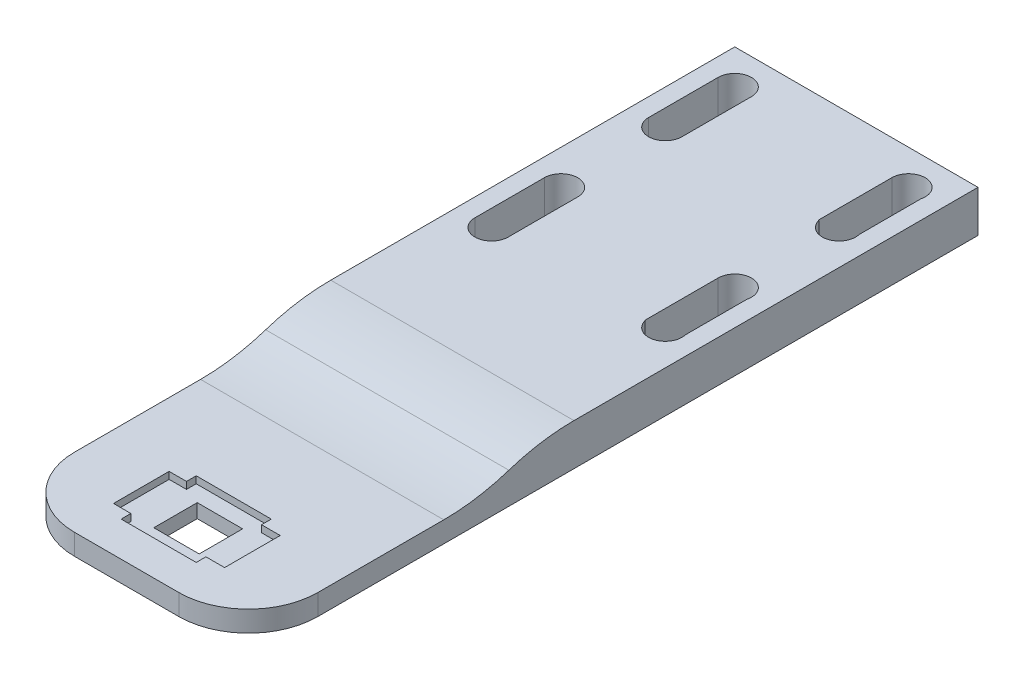
SolidWorks part; units mm, degrees
ref_plane "Front Plane" through (0, 0, 0) normal (0, 0, 1) x (1, 0, 0)
ref_plane "Top Plane" through (0, 0, 0) normal (0, 1, 0) x (1, 0, 0)
ref_plane "Right Plane" through (0, 0, 0) normal (1, 0, 0) x (0, 0, -1)
sketch "Sketch1" plane through (0, 0, 0) normal (0, 1, 0) x (1, 0, 0)
  line L1 (-17.3881, 19.9254) -> (17.6119, 19.9254)
  line L2 (-17.3881, 19.9254) -> (-17.3881, -85.0746)
  line L3 (-17.3881, -85.0746) -> (17.6119, -85.0746)
  line L4 (17.6119, 19.9254) -> (17.6119, -85.0746)
  dimension "D1" = 35
  dimension "D2" = 105
extrude "Boss-Extrude1" add sketch "Sketch1" along normal blind 6
sketch "Sketch2" plane through (0, 6, 0) normal (0, 1, 0) x (1, 0, 0)
  line L0 (17.6119, 19.9254) -> (-17.3881, 19.9254) construction
  line L1 (12.6119, -10.0746) -> (-12.3881, -10.0746)
  line L2 (12.6119, -10.0746) -> (12.6119, 14.9254)
  line L3 (12.6119, 14.9254) -> (-12.3881, 14.9254)
  line L4 (-12.3881, -10.0746) -> (-12.3881, 14.9254)
  line L5 (12.6119, -10.0746) -> (-12.3881, 14.9254) construction
  line L6 (12.6119, 14.9254) -> (-12.3881, -10.0746) construction
  point P0 (0.1119, 2.4254)
  point P7 (0.1119, 19.9254)
  dimension "D1" = 25
  dimension "D2" = 25
  dimension "D3" = 0
  dimension "D4" = 5
hole_wizard "M4 Clearance Hole1" positions "Sketch3" profile "Sketch4" hole size "M4" standard "ANSI Metric" end condition through all
sketch "Sketch3" plane through (0, 6, 0) normal (0, 1, 0) x (1, 0, 0)
  point P0 (-12.3881, 14.9254)
  point P3 (12.6119, 14.9254)
  point P6 (12.6119, -10.0746)
  point P9 (-12.3881, -10.0746)
sketch "Sketch4" plane through (-12.3881, 6, -14.9254) normal (1, 0, 0) x (0, 0, 1)
  line L0 (0, 0) -> (0, 6)
  line L1 (0, 6) -> (2.4, 6)
  line L2 (2.4, 6) -> (2.4, 0)
  line L5 (2.4, 0) -> (0, 0)
  line L11 (0, -6.35) -> (0, 107.95) construction
  dimension "Thru Hole Dia." = 4.8
  dimension "Thru Hole Depth" = 6
pattern_linear "LPattern2" count 2 spacing 10 along (0, 0, 1) of "M4 Clearance Hole1"
sketch "Sketch5" plane through (0, 6, 0) normal (0, 1, 0) x (1, 0, 0)
  line L1 (-14.7881, 14.9254) -> (-9.9881, 14.9254)
  line L2 (-14.7881, 14.9254) -> (-14.7881, 4.9254)
  line L3 (-14.7881, 4.9254) -> (-9.9881, 4.9254)
  line L4 (-9.9881, 14.9254) -> (-9.9881, 4.9254)
  line L5 (-14.7881, -10.0746) -> (-9.9881, -10.0746)
  line L6 (-14.7881, -10.0746) -> (-14.7881, -20.0746)
  line L7 (-14.7881, -20.0746) -> (-9.9881, -20.0746)
  line L8 (-9.9881, -10.0746) -> (-9.9881, -20.0746)
  line L9 (10.2119, 14.9254) -> (14.9426, 14.9254)
  line L10 (10.2119, 14.9254) -> (10.2119, 4.3527)
  line L11 (10.2119, 4.3527) -> (14.9426, 4.3527)
  line L12 (14.9426, 14.9254) -> (14.9426, 4.3527)
  line L13 (10.2119, -10.0746) -> (14.9426, -10.0746)
  line L14 (10.2119, -10.0746) -> (10.2119, -20.6473)
  line L15 (10.2119, -20.6473) -> (14.9426, -20.6473)
  line L16 (14.9426, -10.0746) -> (14.9426, -20.6473)
  circle A0 centre (-12.3881, 14.9254) radius 2.4 construction
  circle A1 centre (-12.3881, 4.9254) radius 2.4 construction
  circle A2 centre (-12.3881, -10.0746) radius 2.4 construction
  circle A3 centre (-12.3881, -20.0746) radius 2.4 construction
  circle A4 centre (12.6119, 14.9254) radius 2.4 construction
  circle A5 centre (12.6119, 4.9254) radius 2.4 construction
  circle A6 centre (12.6119, -10.0746) radius 2.4 construction
  circle A7 centre (12.6119, -20.0746) radius 2.4 construction
extrude "Cut-Extrude1" cut sketch "Sketch5" against normal through all
sketch "Sketch6" plane through (0, 6, 0) normal (0, 1, 0) x (1, 0, 0)
  line L1 (5.1119, -80.0746) -> (-5.6881, -80.0746)
  line L2 (5.1119, -80.0746) -> (5.1119, -69.2746)
  line L3 (5.1119, -69.2746) -> (-5.6881, -69.2746)
  line L4 (-5.6881, -80.0746) -> (-5.6881, -69.2746)
  line L5 (5.1119, -80.0746) -> (-5.6881, -69.2746) construction
  line L6 (5.1119, -69.2746) -> (-5.6881, -80.0746) construction
  line L9 (-17.3881, -85.0746) -> (17.6119, -85.0746) construction
  point P0 (-0.2881, -74.6746)
  dimension "D1" = 10.8
  dimension "D2" = 10.8
  dimension "D3" = 5
extrude "Cut-Extrude2" cut sketch "Sketch6" against normal offset from surface (4 mm away) 2 up to face at (-12.3881, 0, 15.0746)
sketch "Sketch7" plane through (0, 2, 0) normal (0, 1, 0) x (1, 0, 0)
  line L0 (5.1119, -80.0746) -> (5.1119, -69.2746) construction
  line L1 (3.2656, -77.8005) -> (-3.2656, -77.8005)
  line L2 (3.2656, -77.8005) -> (3.2656, -71.5487)
  line L3 (3.2656, -71.5487) -> (-3.2656, -71.5487)
  line L4 (-3.2656, -77.8005) -> (-3.2656, -71.5487)
  line L5 (3.2656, -77.8005) -> (-3.2656, -71.5487) construction
  line L6 (3.2656, -71.5487) -> (-3.2656, -77.8005) construction
  point P0 (0, -74.6746)
  point P7 (5.1119, -74.6746)
  dimension "D1" = 0
extrude "Cut-Extrude3" cut sketch "Sketch7" against normal through all
sketch "Sketch8" plane through (0, 6, 0) normal (0, 1, 0) x (1, 0, 0)
  line L0 (5.1119, -80.0746) -> (5.1119, -69.2746) construction
  line L1 (7.7965, -78.6746) -> (-8.1881, -78.6746)
  line L2 (7.7965, -78.6746) -> (7.7965, -70.6746)
  line L3 (7.7965, -70.6746) -> (-8.1881, -70.6746)
  line L4 (-8.1881, -78.6746) -> (-8.1881, -70.6746)
  line L5 (7.7965, -78.6746) -> (-8.1881, -70.6746) construction
  line L6 (7.7965, -70.6746) -> (-8.1881, -78.6746) construction
  line L7 (-5.6881, -69.2746) -> (-5.6881, -80.0746) construction
  point P0 (-0.1958, -74.6746)
  point P7 (5.1119, -74.6746)
  dimension "D1" = 0
  dimension "D2" = 2.5
  dimension "D3" = 8
extrude "Cut-Extrude4" cut sketch "Sketch8" against normal up to surface (4 mm away) up to face at (0, 2, 74.6746)
fillet "Fillet1" radius 10 2 edges at (17.6119, 3, 85.0746) (-17.3881, 3, 85.0746)
sketch "Sketch9" plane through (0, 0, 0) normal (0, -1, 0) x (1, 0, 0)
  line L0 (-17.3881, -19.9254) -> (-17.3881, 75.0746) construction
  line L1 (-17.3881, 43.8746) -> (19.6619, 43.8746)
  line L2 (-17.3881, 43.8746) -> (-17.3881, 85.0746)
  line L3 (-17.3881, 85.0746) -> (19.6619, 85.0746)
  line L4 (19.6619, 43.8746) -> (19.6619, 85.0746)
  line L5 (-7.3881, 85.0746) -> (7.6119, 85.0746) construction
  line L6 (5.1119, 69.2746) -> (-5.6881, 69.2746) construction
  dimension "D1" = 25.4
  dimension "D2" = 0
extrude "Cut-Extrude5" cut sketch "Sketch9" along normal offset from surface (3 mm away) 3 from surface up to face at (0, 0, 74.6746) starting at face at (-0.2573, 6, 74.6746)
fillet "Fillet2" radius 30 1 edges at (0.1119, 3, 43.8746)
fillet "Fillet3" radius 30 1 edges at (0.1119, 6, 43.8746)
